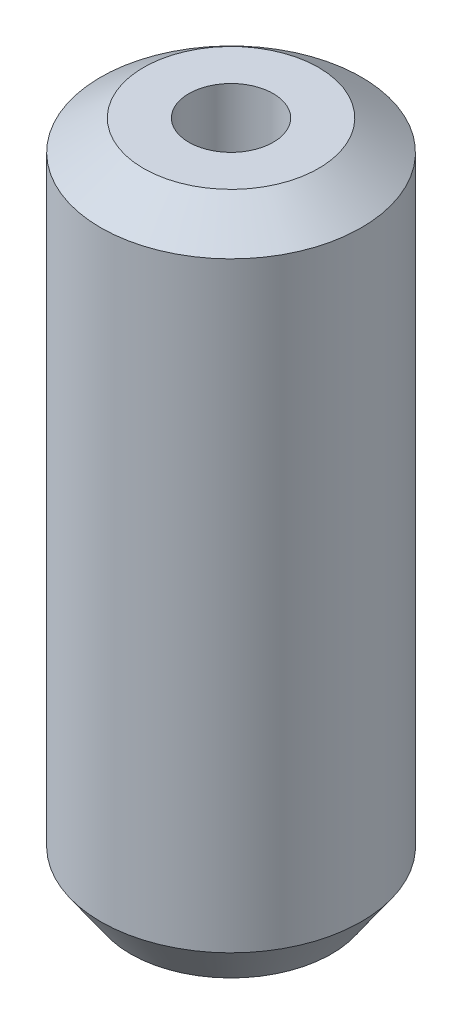
SolidWorks part; units mm, degrees
ref_plane "Front Plane" through (0, 0, 0) normal (0, 0, 1) x (1, 0, 0)
ref_plane "Top Plane" through (0, 0, 0) normal (0, 1, 0) x (1, 0, 0)
ref_plane "Right Plane" through (0, 0, 0) normal (1, 0, 0) x (0, 0, -1)
sketch "Sketch1" plane through (0, 0, 0) normal (0, 1, 0) x (1, 0, 0)
  circle A0 centre (0, 0) radius 7.5
  dimension "SHAFT_OD" = 15
extrude "Boss-Extrude1" add sketch "Sketch1" along normal blind 38.7494
sketch "Sketch2" plane through (0, 0, 0) normal (0, 1, 0) x (1, 0, 0)
  circle A0 centre (0, 0) radius 2.4275
  dimension "BORE_D" = 4.8551
extrude "Cut-Extrude1" cut sketch "Sketch2" along normal through all
chamfer "Chamfer1" distance 1.7168 angle 55.155 2 edges at (0, 38.7494, 7.5) (0, 0, 7.5) first distance on face at (0, 38.7494, 7.5) first distance on face at (0, 0, 2.4275)
